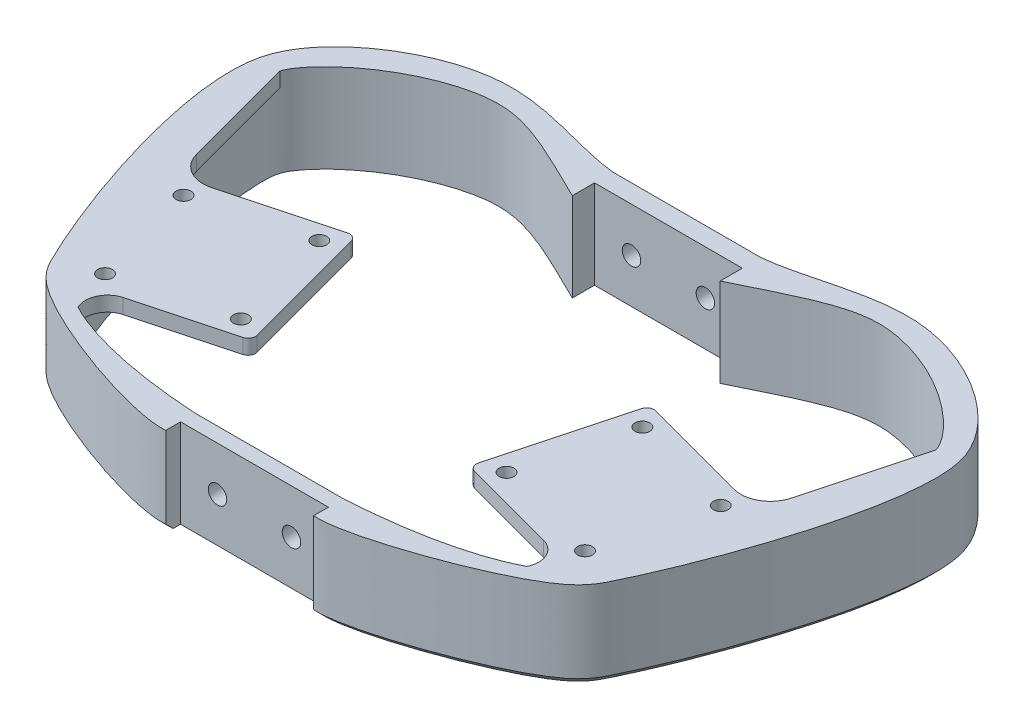
SolidWorks part; units mm, degrees
ref_plane "Спереди" through (0, 0, 0) normal (0, 0, 1) x (1, 0, 0)
ref_plane "Сверху" through (0, 0, 0) normal (0, 1, 0) x (1, 0, 0)
ref_plane "Справа" through (0, 0, 0) normal (1, 0, 0) x (0, 0, -1)
sketch "Эскиз1" plane through (0, 0, 0) normal (0, 1, 0) x (1, 0, 0)
  line L0 (-18.5282, 70.6531) -> (-18.5282, 65.1531) construction
  line L2 (-5.9856, 70.6531) -> (-45, 70.6531) construction
  line L3 (-45, 0) -> (0, 0) construction
  line L4 (-8.5282, 70.6531) -> (-8.5282, 68.1531)
  line L5 (-18.5282, 65.1531) -> (-18.5282, 68.1531)
  line L6 (-18.5282, 68.1531) -> (-8.5282, 68.1531)
  line L7 (-52.9117, 59.9767) -> (-42.5589, 21.3397) construction
  line L8 (-42.5589, 21.3397) -> (-23.2404, 26.5161) construction
  line L9 (-23.2404, 26.5161) -> (-33.5932, 65.1531) construction
  line L10 (-33.5932, 65.1531) -> (-52.9117, 59.9767) construction
  line L11 (-45, 70.6531) -> (-41, 70.6531) construction
  line L13 (-23.5282, 34.5441) -> (-23.5282, 14.7202) construction
  line L14 (-18.5282, 70.6531) -> (-8.5282, 70.6531)
  line L15 (-36.9927, 60.2786) -> (-36.9927, 70.6531) construction
  line L16 (-18.5282, 68.1531) -> (-18.5282, 10.1531) construction
  line L17 (-18.5282, 10.1531) -> (-18.5282, 14.1531) construction
  line L19 (-36.9927, 70.6531) -> (-36.9927, 73.6531) construction
  line L20 (-8.5282, 68.1531) -> (-8.5282, 12.1531) construction
  line L21 (-8.5282, 14.1531) -> (-8.5282, 12.1531)
  line L22 (-8.5282, 14.1531) -> (-18.5282, 14.1531)
  line L23 (-8.5282, 12.1531) -> (-18.5282, 12.1531)
  line L25 (-18.5282, 12.1531) -> (-18.5282, 10.1531)
  spline S0 degree 3 poles (-18.5282, 14.1531) (-27.6517, 14.6822) (-39.6543, 17.2222) (-49.0697, 29.7277) (-54.02, 56.3393) (-52.3007, 62.3964) (-44.8154, 68.9517) (-31.8295, 71.8573) (-26.6401, 69.1254) (-18.5282, 65.1531) knots 0 0 0 0 0.169509 0.225658 0.524174 0.588058 0.800611 0.844462 1 1 1 1
  spline S1 degree 3 poles (-18.5282, 10.1531) (-23.0338, 9.7383) (-43.4067, 16.9249) (-49.6135, 28.683) (-57.3433, 50.2105) (-55.2196, 66.1298) (-37.4394, 77.6326) (-24.2855, 71.2513) (-18.5282, 70.6531) knots 0 0 0 0 0.145181 0.201011 0.518599 0.583099 0.806305 1 1 1 1
  dimension "D6" = 70.6531
  dimension "D7" = 3
  dimension "D4" = 15
  dimension "D2" = 5.5
  dimension "D9" = 3
  dimension "D10" = 10
  dimension "D11" = 54
extrude "Бобышка-Вытянуть1" add sketch "Эскиз1" along normal blind 12
sketch "Эскиз6" plane through (0, 12, 0) normal (0, 1, 0) x (1, 0, 0)
  line L0 (-36.972, 22.8367) -> (-24.2063, 26.2573)
  line L1 (-23.4992, 27.482) -> (-28.158, 44.8687)
  line L2 (-29.3827, 45.5758) -> (-43.8716, 41.6935)
  line L3 (-52.9117, 59.9767) -> (-42.5589, 21.3397) construction
  line L4 (-42.5589, 21.3397) -> (-23.2404, 26.5161) construction
  line L7 (-52.9117, 59.9767) -> (-55.4599, 57.4285)
  line L8 (-55.4599, 57.4285) -> (-45.108, 21.7125)
  line L9 (-44.5427, 21.0722) -> (-38.9026, 18.646)
  line L10 (-52.9117, 59.9767) -> (-48.7706, 44.5219)
  line L17 (-45, 0) -> (0, 0) construction
  line L21 (-52.9117, 59.9767) -> (-42.5589, 21.3397) construction
  line L22 (-42.5589, 21.3397) -> (-23.2404, 26.5161) construction
  line L23 (-23.2404, 26.5161) -> (-33.5932, 65.1531) construction
  line L24 (-33.5932, 65.1531) -> (-52.9117, 59.9767) construction
  line L25 (-45, 70.6531) -> (-41, 70.6531) construction
  line L29 (-36.9927, 60.2786) -> (-36.9927, 70.6531) construction
  line L30 (-12.5082, 2.074) -> (-13.6653, 3.7053)
  line L31 (-36.9927, 70.6531) -> (-36.9927, 73.6531) construction
  arc A0 (-36.972, 22.8367) -> (-38.9026, 18.646) centre (-36.1956, 19.9389) ccw
  arc A1 (-43.8716, 41.6935) -> (-48.7706, 44.5219) centre (-44.9069, 45.5572) cw
  arc A2 (-24.2063, 26.2573) -> (-23.4992, 27.482) centre (-24.4652, 27.2232) ccw
  arc A3 (-28.158, 44.8687) -> (-29.3827, 45.5758) centre (-29.1239, 44.6098) ccw
  arc A4 (-45.108, 21.7125) -> (-44.5427, 21.0722) centre (-44.1476, 21.9908) ccw
  spline S0 degree 3 poles (-18.5282, 14.1531) (-27.6517, 14.6822) (-39.6543, 17.2222) (-49.0697, 29.7277) (-54.02, 56.3393) (-52.3007, 62.3964) (-44.8154, 68.9517) (-31.8295, 71.8573) (-26.6401, 69.1254) (-18.5282, 65.1531) knots 0 0 0 0 0.169509 0.225658 0.524174 0.588058 0.800611 0.844462 1 1 1 1 construction
  point P17 (-47.7353, 40.6582)
  point P30 (-23.2404, 26.5161)
  point P36 (-28.4168, 45.8346)
  spline M3 degree 3 poles (-18.5282, 14.1531) (-27.6517, 14.6822) (-39.6543, 17.2222) (-49.0697, 29.7277) (-54.02, 56.3393) (-52.3007, 62.3964) (-44.8154, 68.9517) (-31.8295, 71.8573) (-26.6401, 69.1254) (-18.5282, 65.1531) knots 0 0 0 0 0.169509 0.225658 0.524174 0.588058 0.800611 0.844462 1 1 1 1
  dimension "D1" = 3
  dimension "D2" = 4
  dimension "D3" = 1
  dimension "D4" = 20
  dimension "D6" = 2
  dimension "D9" = 45
  dimension "D13" = 3
extrude "Бобышка-Вытянуть2" add sketch "Эскиз6" against normal blind 2 contours L1 A3 L2 A1 L10 A0 L0 A2 M3
sketch "Эскиз13" plane through (0, 10, 0) normal (0, -1, 0) x (-1, 0, 0)
  circle A0 centre (30.3799, 42.7727) radius 1
  circle A1 centre (26.4976, 28.2838) radius 1
  circle A2 centre (40.9865, 24.4016) radius 1
  circle A3 centre (44.8688, 38.8904) radius 1
sketch "Эскиз12" plane through (0, 0, -70.6531) normal (0, 0, -1) x (-1, 0, 0)
  line L0 (8.5282, 6) -> (13.5282, 6) construction
  line L1 (8.5282, 12) -> (8.5282, 0) construction
  circle A0 centre (13.5282, 6) radius 1.25
extrude "Вырез-Вытянуть5" cut sketch "Эскиз12" against normal through all
extrude "Вырез-Вытянуть6" cut sketch "Эскиз13" against normal blind 10
mirror "Зеркальное отражение1" about plane through (-8.5282, 12, 0) normal (1, 0, 0) of bodies 121 119
chamfer "Фаска2" distance 1 angle 45 3 edges at (-8.5282, 0, -70.6531)
sketch "Эскиз14" plane through (0, 0, -14.1531) normal (0, 0, -1) x (-1, 0, 0)
  line L0 (13.5282, 3.5) -> (3.5282, 3.5)
  line L1 (13.5282, 8.5) -> (3.5282, 8.5)
  arc A0 (13.5282, 3.5) -> (13.5282, 8.5) centre (13.5282, 6) ccw
  arc A1 (3.5282, 8.5) -> (3.5282, 3.5) centre (3.5282, 6) ccw
  circle A2 centre (13.5282, 6) radius 1.25
  circle A3 centre (3.5282, 6) radius 1.25
extrude "Бобышка-Вытянуть3" add sketch "Эскиз14" along normal blind 2
fillet "Скругление1" radius 2.5 4 edges at (-16.0282, 6, -14.1531) (-8.5282, 3.5, -14.1531) (-1.0282, 6, -14.1531) (-8.5282, 8.5, -14.1531)
